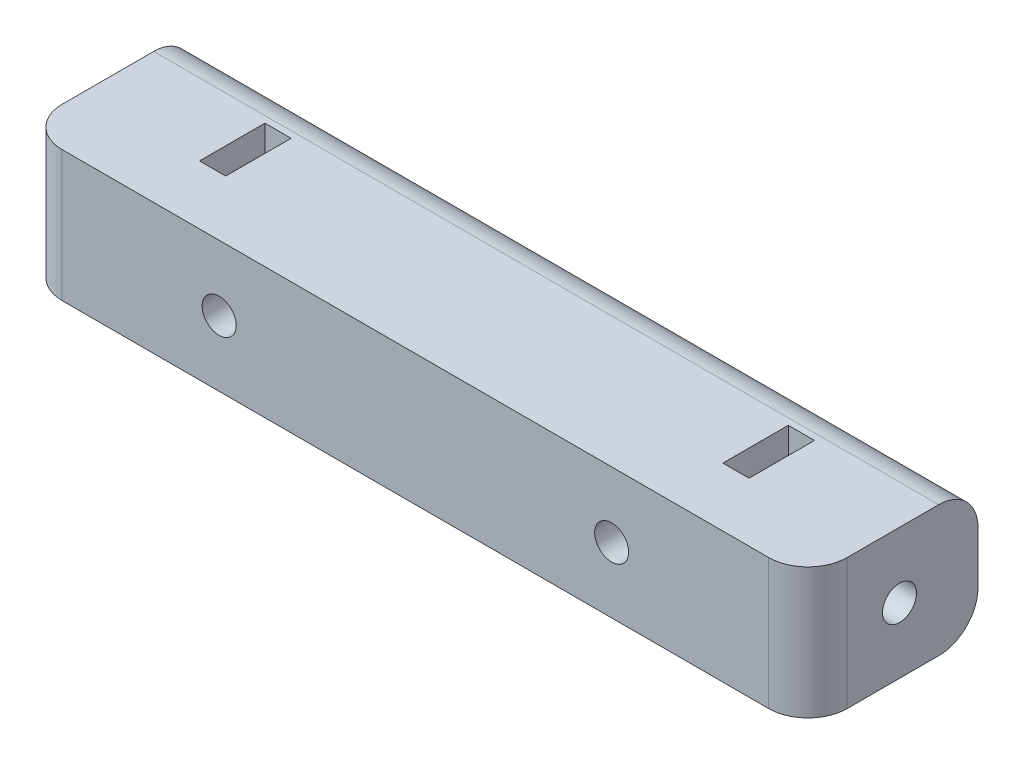
SolidWorks part; units mm, degrees
ref_plane "Front Plane" through (0, 0, 0) normal (0, 0, 1) x (1, 0, 0)
ref_plane "Top Plane" through (0, 0, 0) normal (0, 1, 0) x (1, 0, 0)
ref_plane "Right Plane" through (0, 0, 0) normal (1, 0, 0) x (0, 0, -1)
sketch "Sketch2" plane through (0, 0, 0) normal (0, 0, 1) x (1, 0, 0)
  line L1 (-30, 5) -> (30, 5)
  line L2 (-30, 5) -> (-30, -5)
  line L3 (-30, -5) -> (30, -5)
  line L4 (30, 5) -> (30, -5)
  line L5 (-30, 5) -> (30, -5) construction
  line L6 (-30, -5) -> (30, 5) construction
  point P0 (0, 0)
  dimension "D1" = 10
  dimension "D2" = 60
extrude "Boss-Extrude1" add sketch "Sketch2" along normal blind 13
sketch "Sketch3" plane through (0, 0, 0) normal (0, 0, -1) x (-1, 0, 0)
  line L0 (-15, 0) -> (15, 0) construction
  line L1 (-15, -3) -> (-12.4019, -1.5)
  line L2 (-12.4019, -1.5) -> (-12.4019, 1.5)
  line L3 (-12.4019, 1.5) -> (-15, 3)
  line L4 (-15, 3) -> (-17.5981, 1.5)
  line L5 (-17.5981, 1.5) -> (-17.5981, -1.5)
  line L6 (-17.5981, -1.5) -> (-15, -3)
  line L7 (15, -3) -> (17.5981, -1.5)
  line L8 (17.5981, -1.5) -> (17.5981, 1.5)
  line L9 (17.5981, 1.5) -> (15, 3)
  line L10 (15, 3) -> (12.4019, 1.5)
  line L11 (12.4019, 1.5) -> (12.4019, -1.5)
  line L12 (12.4019, -1.5) -> (15, -3)
  circle A0 centre (-15, 0) radius 2.5981 construction
  circle A1 centre (15, 0) radius 2.5981 construction
  point P9 (0, 0)
  dimension "D1" = 30
  dimension "D2" = 6
extrude "Cut-Extrude1" cut sketch "Sketch3" against normal blind 3
sketch "Sketch4" plane through (0, 0, 3) normal (0, 0, -1) x (-1, 0, 0)
  line L0 (-15, 3) -> (-15, -3) construction
  line L1 (-12.4019, 1.5) -> (-15, 3) construction
  line L2 (-12.4019, 1.5) -> (-15, 3) construction
  line L3 (-17.5981, -1.5) -> (-15, -3) construction
  line L4 (-17.5981, -1.5) -> (-15, -3) construction
  line L5 (15, 3) -> (15, -3) construction
  circle A0 centre (-15, 0) radius 1.3
  circle A1 centre (15, 0) radius 1.3
  dimension "D1" = 2.6
extrude "Cut-Extrude2" cut sketch "Sketch4" against normal through all
fillet "Fillet1" radius 3 2 edges at (0, -5, 0) (0, 5, 0)
fillet "Fillet2" radius 3 2 edges at (-30, 0, 13) (30, 0, 13)
sketch "Sketch5" plane through (30, 0, 0) normal (1, 0, 0) x (0, 0, -1)
  circle A0 centre (-6, 0) radius 1.3
  dimension "D1" = 2.6
  dimension "D2" = 7
extrude "Cut-Extrude3" cut sketch "Sketch5" against normal blind 10
sketch "Sketch6" plane through (0, 5, 0) normal (0, 1, 0) x (1, 0, 0)
  line L0 (30, -10) -> (30, -3) construction
  line L1 (19, -3.5) -> (21, -3.5)
  line L2 (19, -3.5) -> (19, -8.5)
  line L3 (19, -8.5) -> (21, -8.5)
  line L4 (21, -3.5) -> (21, -8.5)
  line L5 (19, -3.5) -> (21, -8.5) construction
  line L6 (19, -8.5) -> (21, -3.5) construction
  line L7 (27, -13) -> (-27, -13) construction
  point P0 (20, -6)
  dimension "D1" = 5
  dimension "D2" = 2
  dimension "D3" = 10
  dimension "D4" = 7
extrude "Cut-Extrude4" cut sketch "Sketch6" against normal through all both and the other way through all
mirror "Mirror1" about plane through (0, 0, 0) normal (1, 0, 0) of "Cut-Extrude4", "Cut-Extrude3"
